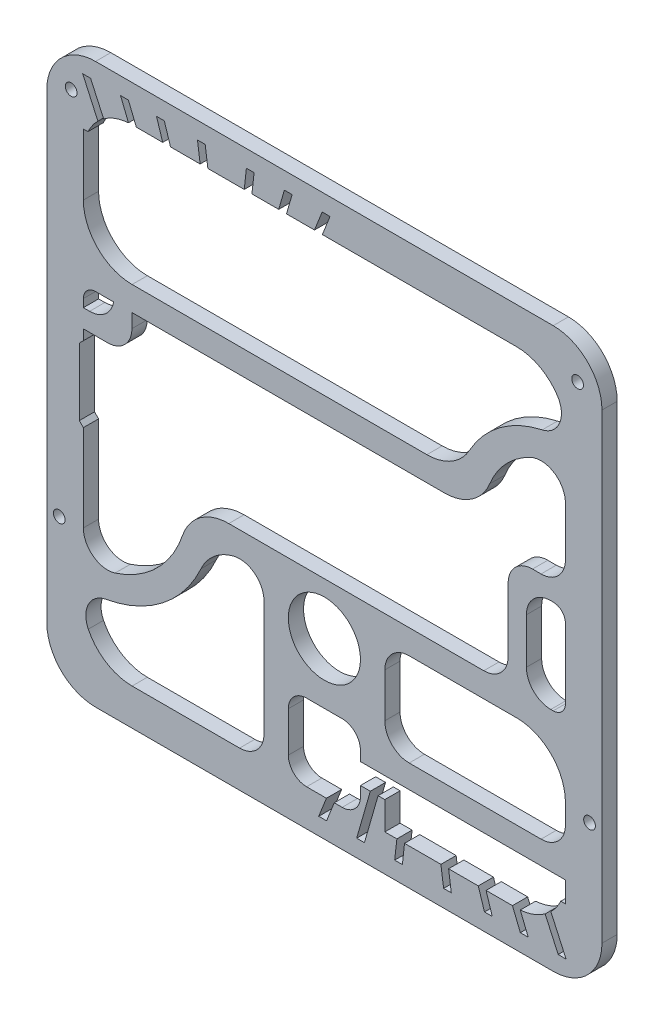
SolidWorks part; units mm, degrees
ref_plane "Front Plane" through (0, 0, 0) normal (0, 0, 1) x (1, 0, 0)
ref_plane "Top Plane" through (0, 0, 0) normal (0, 1, 0) x (1, 0, 0)
ref_plane "Right Plane" through (0, 0, 0) normal (1, 0, 0) x (0, 0, -1)
sketch "Sketch1" plane through (0, 0, 0) normal (0, 0, 1) x (1, 0, 0)
  line L0 (44.642, 21.8842) -> (44.642, 18.0742) construction
  line L1 (-8.1388, 21.8842) -> (49.7286, 21.8842)
  line L2 (-8.1388, 21.8842) -> (-8.1388, -36.406)
  line L3 (-8.1388, -36.406) -> (49.7286, -36.406)
  line L4 (49.7286, 21.8842) -> (49.7286, -36.406)
  line L5 (45.9186, -32.596) -> (-4.3288, -32.596)
  line L6 (45.9186, -32.596) -> (45.9186, 18.0742)
  line L7 (45.9186, 18.0742) -> (-4.3288, 18.0742)
  line L8 (-4.3288, -32.596) -> (-4.3288, 18.0742)
  line L9 (44.642, 19.9792) -> (-35.1587, 19.9792) construction
  line L10 (-4.3288, -31.0517) -> (-8.1388, -31.0517) construction
  line L11 (-6.2338, -31.0517) -> (-6.2338, 6.9585) construction
  line L12 (20.6521, 19.9792) -> (21.1982, 19.9792) construction
  line L13 (-6.2338, -12.887) -> (-6.2338, -25.1298) construction
  line L14 (3.0779, -32.596) -> (3.0779, -36.406) construction
  line L15 (3.0779, -34.501) -> (37.3423, -34.501) construction
  line L17 (49.7286, 15.2205) -> (45.9186, 15.2205) construction
  line L18 (47.8236, 15.2205) -> (47.8236, -0.9437) construction
  line L19 (47.8236, -1.6348) -> (47.8236, 10.608) construction
  line L20 (20.9378, -34.501) -> (20.3916, -34.501) construction
  dimension "D1" = 3.81
  dimension "D2" = 3.81
extrude "Boss-Extrude1" add sketch "Sketch1" along normal blind 1.5875
sketch "Sketch2" plane through (0, 0, 0) normal (0, 0, -1) x (-1, 0, 0)
  line L0 (-45.9186, -32.596) -> (-45.9186, 18.0742) construction
  line L1 (-34.8696, 3.653) -> (4.3288, 3.653)
  line L2 (-45.9186, 3.653) -> (-45.9186, 0.7339)
  line L3 (-37.4096, 1.113) -> (4.3288, 1.113)
  line L4 (4.3288, 3.653) -> (4.3288, 1.113)
  line L5 (4.3288, 18.0742) -> (4.3288, -32.596) construction
  line L6 (-33.4496, 1.113) -> (-36.4496, 1.113) construction
  line L7 (1.2504, -12.887) -> (-36.4496, -12.887) construction
  line L8 (-45.9186, -15.427) -> (-8.8785, -15.427)
  line L9 (-45.9186, -15.427) -> (-45.9186, -12.887)
  line L10 (-45.9186, -12.887) -> (-6.5805, -12.887)
  line L11 (1.357, -21.2563) -> (14.2432, -21.2563) construction
  line L12 (4.3288, -23.7963) -> (4.3288, -26.3363)
  line L13 (-45.9186, 12.162) -> (-45.9186, 9.622)
  arc A0 (-45.9186, 9.622) -> (-37.4096, 1.113) centre (-45.9186, 1.113) cw
  arc A1 (-45.9186, 12.162) -> (-34.8696, 3.653) centre (-45.9186, 0.7339) cw
  arc A2 (4.3288, -23.7963) -> (-6.5805, -12.887) centre (4.3288, -12.887) cw
  arc A3 (-8.8785, -15.427) -> (4.3288, -26.3363) centre (4.3288, -12.887) ccw
  circle A5 centre (1.357, -18.2591) radius 2.9972 construction
  line M5 (-45.9186, -32.596) -> (-45.9186, 18.0742)
  line M7 (4.3288, 18.0742) -> (4.3288, -32.596)
  dimension "D5" = 2.54
  dimension "D1" = 2.54
  dimension "D2" = 2.54
  dimension "D3" = 2.54
  dimension "D4" = 2.54
  dimension "D6" = 2.54
  dimension "D7" = 2.54
extrude "Boss-Extrude2" add sketch "Sketch2" against normal up to surface (1.5875 mm away) contours A1 A0 L3 L1 M5 M7 | L10 L8 M5 M7 region at (15.2704, 3.1385, 0) region at (-3.8086, -25.0663, 0) up to face at (20.7949, -7.2609, 1.5875)
sketch "Sketch3" plane through (0, 0, 0) normal (0, 0, -1) x (-1, 0, 0)
  line L0 (-45.9186, -1.1649) -> (-39.9496, -1.1649)
  line L1 (-45.9186, -12.887) -> (-45.9186, 9.622) construction
  line L2 (-39.9496, -4.387) -> (-39.9496, -11.387) construction
  line L3 (-39.9496, -1.1649) -> (-39.9496, -12.887)
  line L4 (-45.9186, -12.887) -> (-6.5805, -12.887) construction
  line L5 (-39.9496, -12.887) -> (-41.8546, -12.887)
  line L6 (-41.8546, -12.887) -> (-41.8546, -3.0699)
  line L7 (-41.8546, -3.0699) -> (-45.9186, -3.0699)
  line L8 (-45.9186, -3.0699) -> (-45.9186, -1.1649)
  line L9 (-42.9468, 0.7401) -> (-53.4831, 0.7401) construction
  line L10 (-0.7296, 1.113) -> (-0.7296, -2.887)
  line L11 (-37.4096, 1.113) -> (4.3288, 1.113) construction
  line L12 (-1.9996, -2.887) -> (1.2504, -2.887) construction
  line L13 (-0.7296, -2.887) -> (4.3288, -2.887)
  line L14 (4.3288, 1.113) -> (4.3288, -23.7963) construction
  line L15 (4.3288, -2.887) -> (4.3288, -0.982)
  line L16 (4.3288, -0.982) -> (1.1754, -0.982)
  line L17 (1.1754, -0.982) -> (1.1754, 1.113)
  line L18 (1.1754, 1.113) -> (-0.7296, 1.113)
  circle A0 centre (-42.9468, 3.7373) radius 2.9972 construction
  dimension "D1" = 1.905
  dimension "D2" = 1.905
  dimension "D3" = 1.905
  dimension "D4" = 1.905
  dimension "D5" = 1.27
  dimension "D6" = 1.905
extrude "Boss-Extrude3" add sketch "Sketch3" against normal up to surface (1.5875 mm away) up to face at (21.2778, -6.3699, 1.5875)
fillet "Fillet1" radius 5.08 4 edges at (49.7286, -36.406, 0.7937) (-8.1388, -36.406, 0.7937) (-8.1388, 21.8842, 0.7937) (49.7286, 21.8842, 0.7937)
fillet "Fillet2" radius 5.08 10 edges at (8.8785, -15.427, 0.7937) (45.9186, -15.427, 0.7937) (45.9186, -32.596, 0.7937) (-4.3288, -32.596, 0.7937) (34.8696, 3.653, 0.7937) (-4.3288, 3.653, 0.7937) (45.9186, 18.0742, 0.7937) (-4.3288, 18.0742, 0.7937) (6.5805, -12.887, 0.7937) (37.4096, 1.113, 0.7937)
fillet "Fillet3" radius 2.54 11 edges at (41.8546, -3.0699, 0.7938) (39.9496, -12.887, 0.7938) (41.8546, -12.887, 0.7938) (39.9496, -1.1649, 0.7938) (45.9186, -1.1649, 0.7938) (-1.1754, -0.982, 0.7938) (0.7296, -2.887, 0.7938) (45.9186, 9.622, 0.7937) (-4.3288, -26.3363, 0.7937) (-4.3288, -23.7963, 0.7937) (45.9186, 12.162, 0.7937)
fillet "Fillet4" radius 1.27 3 edges at (45.9186, -12.887, 0.7937) (45.9186, -3.0699, 0.7938) (-4.3288, 1.113, 0.7937)
sketch "Sketch5" plane through (0, 0, 0) normal (0, 0, -1) x (-1, 0, 0)
  line L0 (-40.8386, -15.427) -> (-12.5612, -15.427) construction
  line L1 (-27.0941, -15.427) -> (-14.4957, -15.427)
  line L2 (-27.0941, -15.427) -> (-27.0941, -32.596)
  line L3 (-27.0941, -32.596) -> (-14.4957, -32.596)
  line L4 (-14.4957, -15.427) -> (-14.4957, -32.596)
  line L5 (-0.7512, -32.596) -> (-40.8386, -32.596) construction
  line L6 (-24.5541, -18.2972) -> (-27.0941, -18.2972) construction
  line L9 (-17.0357, -18.2972) -> (-14.4957, -18.2972) construction
  circle A1 centre (-20.7949, -18.2972) radius 3.7592 construction
  dimension "D1" = 2.54
extrude "Boss-Extrude4" add sketch "Sketch5" against normal up to surface (1.5875 mm away) up to face at (-3.29, -0.0173, 1.5875)
sketch "Sketch6" plane through (0, 0, 0) normal (0, 0, -1) x (-1, 0, 0)
  circle A0 centre (-20.7949, -18.2972) radius 3.7592 construction
  circle A1 centre (-20.7949, -18.2972) radius 3.7592
extrude "Cut-Extrude2" cut sketch "Sketch6" against normal up to surface (1.5875 mm away) up to face at (6.2356, -24.4396, 1.5875)
sketch "Sketch7" plane through (0, 0, 0) normal (0, 0, -1) x (-1, 0, 0)
  line L0 (-27.0941, -15.427) -> (-27.0941, -32.596) construction
  line L1 (-24.5541, -24.5964) -> (-17.0357, -24.5964)
  line L2 (-24.5541, -24.5964) -> (-24.5541, -32.596)
  line L3 (-24.5541, -32.596) -> (-17.0357, -32.596)
  line L4 (-17.0357, -24.5964) -> (-17.0357, -32.596)
  line L5 (-14.4957, -32.596) -> (-14.4957, -15.427) construction
  line L6 (-0.7512, -32.596) -> (-14.4957, -32.596) construction
  line L7 (-20.7949, -22.0564) -> (-6.5424, -22.0564) construction
  line L8 (-20.7949, -22.0564) -> (-20.7949, -21.3452) construction
  circle A0 centre (-20.7949, -18.2972) radius 3.7592 construction
  dimension "D1" = 2.54
  dimension "D2" = 2.54
  dimension "D3" = 2.54
extrude "Cut-Extrude3" cut sketch "Sketch7" against normal up to surface (1.5875 mm away) up to face at (24.5541, -18.2972, 1.5875)
fillet "Fillet5" radius 1.905 4 edges at (24.5541, -32.596, 0.7937) (17.0357, -32.596, 0.7938) (17.0357, -24.5964, 0.7938) (24.5541, -24.5964, 0.7938)
sketch "Sketch8" plane through (0, 0, 0) normal (0, 0, -1) x (-1, 0, 0)
  line L0 (-45.9186, -27.516) -> (-45.9186, -20.507) construction
  line L1 (-45.9186, -25.103) -> (-27.0941, -25.103)
  line L2 (-45.9186, -25.103) -> (-45.9186, -27.643)
  line L3 (-45.9186, -27.643) -> (-27.0941, -27.643)
  line L4 (-27.0941, -25.103) -> (-27.0941, -27.643)
  line L5 (-27.0941, -15.427) -> (-27.0941, -32.596) construction
  line L6 (-45.7916, -27.643) -> (-20.3916, -27.643) construction
  dimension "D1" = 2.54
extrude "Boss-Extrude5" add sketch "Sketch8" against normal up to surface (1.5875 mm away) up to face at (20.7949, -28.5962, 1.5875)
fillet "Fillet6" radius 2.54 5 edges at (27.0941, -15.427, 0.7937) (14.4957, -15.427, 0.7937) (14.4957, -32.596, 0.7937) (27.0941, -25.103, 0.7937) (45.9186, -25.103, 0.7937)
sketch "Sketch4" plane through (0, 0, 0) normal (0, 0, -1) x (-1, 0, 0)
  line L0 (3.2504, -2.887) -> (4.7504, -4.387) construction
  line L1 (4.7504, -11.387) -> (3.2504, -12.887) construction
  line L2 (3.2504, -2.887) -> (4.7504, -4.387)
  line L3 (4.7504, -11.387) -> (3.2504, -12.887)
  line L4 (4.7504, -4.387) -> (4.7504, -11.387) construction
  line L5 (4.7504, -4.387) -> (4.7504, -11.387)
  line L6 (3.2504, -2.887) -> (3.2504, -12.887)
  line L32 (4.2018, 13.1212) -> (4.2018, 15.0262)
  line L33 (4.2018, 15.0262) -> (1.9539, 15.0262)
  line L34 (1.9539, 15.0262) -> (4.2018, 19.9792)
  line L35 (4.2018, 19.9792) -> (3.6556, 19.9792)
  line L36 (3.6556, 19.9792) -> (1.4078, 15.0262)
  line L37 (1.4078, 15.0262) -> (-1.7417, 15.0262)
  line L38 (-1.7417, 15.0262) -> (0.2648, 19.9792)
  line L39 (0.2648, 19.9792) -> (-0.2814, 19.9792)
  line L40 (-0.2814, 19.9792) -> (-2.2879, 15.0262)
  line L41 (-2.2879, 15.0262) -> (-5.0437, 15.0262)
  line L42 (-5.0437, 15.0262) -> (-3.469, 19.9792)
  line L43 (-3.469, 19.9792) -> (-4.0152, 19.9792)
  line L44 (-4.0152, 19.9792) -> (-5.5899, 15.0262)
  line L45 (-5.5899, 15.0262) -> (-8.3965, 15.0262)
  line L46 (-8.3965, 15.0262) -> (-7.7108, 19.9792)
  line L47 (-7.7108, 19.9792) -> (-8.257, 19.9792)
  line L48 (-8.257, 19.9792) -> (-8.9427, 15.0262)
  line L49 (-8.9427, 15.0262) -> (-12.2319, 15.0262)
  line L50 (-12.2319, 15.0262) -> (-12.7781, 19.9792)
  line L51 (-12.7781, 19.9792) -> (-13.3242, 19.9792)
  line L52 (-13.3242, 19.9792) -> (-12.7781, 15.0262)
  line L53 (-12.7781, 15.0262) -> (-15.2926, 15.0262)
  line L54 (-15.2926, 15.0262) -> (-16.7151, 19.9792)
  line L55 (-16.7151, 19.9792) -> (-17.2612, 19.9792)
  line L56 (-17.2612, 19.9792) -> (-15.8388, 15.0262)
  line L57 (-15.8388, 15.0262) -> (-18.6963, 15.0262)
  line L58 (-18.6963, 15.0262) -> (-20.6521, 19.9792)
  line L59 (-20.6521, 19.9792) -> (-21.1982, 19.9792)
  line L60 (-21.1982, 19.9792) -> (-19.2425, 15.0262)
  line L61 (-19.2425, 15.0262) -> (-21.1982, 15.0262)
  line L62 (-21.1982, 15.0262) -> (-21.1982, 13.1212)
  line L63 (-21.1982, 13.1212) -> (4.2018, 13.1212)
  line L64 (4.2018, 13.1212) -> (4.2018, 15.0262) construction
  line L65 (4.2018, 15.0262) -> (1.9539, 15.0262) construction
  line L66 (1.9539, 15.0262) -> (4.2018, 19.9792) construction
  line L67 (4.2018, 19.9792) -> (3.6556, 19.9792) construction
  line L68 (3.6556, 19.9792) -> (1.4078, 15.0262) construction
  line L69 (1.4078, 15.0262) -> (-1.7417, 15.0262) construction
  line L70 (-1.7417, 15.0262) -> (0.2648, 19.9792) construction
  line L71 (0.2648, 19.9792) -> (-0.2814, 19.9792) construction
  line L72 (-0.2814, 19.9792) -> (-2.2879, 15.0262) construction
  line L73 (-2.2879, 15.0262) -> (-5.0437, 15.0262) construction
  line L74 (-5.0437, 15.0262) -> (-3.469, 19.9792) construction
  line L75 (-3.469, 19.9792) -> (-4.0152, 19.9792) construction
  line L76 (-4.0152, 19.9792) -> (-5.5899, 15.0262) construction
  line L77 (-5.5899, 15.0262) -> (-8.3965, 15.0262) construction
  line L78 (-8.3965, 15.0262) -> (-7.7108, 19.9792) construction
  line L79 (-7.7108, 19.9792) -> (-8.257, 19.9792) construction
  line L80 (-8.257, 19.9792) -> (-8.9427, 15.0262) construction
  line L81 (-8.9427, 15.0262) -> (-12.2319, 15.0262) construction
  line L82 (-12.2319, 15.0262) -> (-12.7781, 19.9792) construction
  line L83 (-12.7781, 19.9792) -> (-13.3242, 19.9792) construction
  line L84 (-13.3242, 19.9792) -> (-12.7781, 15.0262) construction
  line L85 (-12.7781, 15.0262) -> (-15.2926, 15.0262) construction
  line L86 (-15.2926, 15.0262) -> (-16.7151, 19.9792) construction
  line L87 (-16.7151, 19.9792) -> (-17.2612, 19.9792) construction
  line L88 (-17.2612, 19.9792) -> (-15.8388, 15.0262) construction
  line L89 (-15.8388, 15.0262) -> (-18.6963, 15.0262) construction
  line L90 (-18.6963, 15.0262) -> (-20.6521, 19.9792) construction
  line L91 (-20.6521, 19.9792) -> (-21.1982, 19.9792) construction
  line L92 (-21.1982, 19.9792) -> (-19.2425, 15.0262) construction
  line L93 (-19.2425, 15.0262) -> (-21.1982, 15.0262) construction
  line L94 (-21.1982, 15.0262) -> (-21.1982, 13.1212) construction
  line L95 (-21.1982, 13.1212) -> (4.2018, 13.1212) construction
  line L96 (-45.7916, -27.643) -> (-45.7916, -29.548)
  line L97 (-45.7916, -29.548) -> (-43.5438, -29.548)
  line L98 (-43.5438, -29.548) -> (-45.7916, -34.501)
  line L99 (-45.7916, -34.501) -> (-45.2455, -34.501)
  line L100 (-45.2455, -34.501) -> (-42.9976, -29.548)
  line L101 (-42.9976, -29.548) -> (-39.8482, -29.548)
  line L102 (-39.8482, -29.548) -> (-41.8546, -34.501)
  line L103 (-41.8546, -34.501) -> (-41.3085, -34.501)
  line L104 (-41.3085, -34.501) -> (-39.302, -29.548)
  line L105 (-39.302, -29.548) -> (-36.5462, -29.548)
  line L106 (-36.5462, -29.548) -> (-38.1208, -34.501)
  line L107 (-38.1208, -34.501) -> (-37.5747, -34.501)
  line L108 (-37.5747, -34.501) -> (-36, -29.548)
  line L109 (-36, -29.548) -> (-33.1934, -29.548)
  line L110 (-33.1934, -29.548) -> (-33.879, -34.501)
  line L111 (-33.879, -34.501) -> (-33.3329, -34.501)
  line L112 (-33.3329, -34.501) -> (-32.6472, -29.548)
  line L113 (-32.6472, -29.548) -> (-29.358, -29.548)
  line L114 (-29.358, -29.548) -> (-28.8118, -34.501)
  line L115 (-28.8118, -34.501) -> (-28.2656, -34.501)
  line L116 (-28.2656, -34.501) -> (-28.8118, -29.548)
  line L117 (-28.8118, -29.548) -> (-26.2973, -29.548)
  line L118 (-26.2973, -29.548) -> (-24.8748, -34.501)
  line L119 (-24.8748, -34.501) -> (-24.3286, -34.501)
  line L120 (-24.3286, -34.501) -> (-25.7511, -29.548)
  line L121 (-25.7511, -29.548) -> (-22.8935, -29.548)
  line L122 (-22.8935, -29.548) -> (-20.9378, -34.501)
  line L123 (-20.9378, -34.501) -> (-20.3916, -34.501)
  line L124 (-20.3916, -34.501) -> (-22.3474, -29.548)
  line L125 (-22.3474, -29.548) -> (-20.3916, -29.548)
  line L126 (-20.3916, -29.548) -> (-20.3916, -27.643)
  line L127 (-20.3916, -27.643) -> (-45.7916, -27.643)
  line L128 (-45.7916, -27.643) -> (-45.7916, -29.548) construction
  line L129 (-45.7916, -29.548) -> (-43.5438, -29.548) construction
  line L130 (-43.5438, -29.548) -> (-45.7916, -34.501) construction
  line L131 (-45.7916, -34.501) -> (-45.2455, -34.501) construction
  line L132 (-45.2455, -34.501) -> (-42.9976, -29.548) construction
  line L133 (-42.9976, -29.548) -> (-39.8482, -29.548) construction
  line L134 (-39.8482, -29.548) -> (-41.8546, -34.501) construction
  line L135 (-41.8546, -34.501) -> (-41.3085, -34.501) construction
  line L136 (-41.3085, -34.501) -> (-39.302, -29.548) construction
  line L137 (-39.302, -29.548) -> (-36.5462, -29.548) construction
  line L138 (-36.5462, -29.548) -> (-38.1208, -34.501) construction
  line L139 (-38.1208, -34.501) -> (-37.5747, -34.501) construction
  line L140 (-37.5747, -34.501) -> (-36, -29.548) construction
  line L141 (-36, -29.548) -> (-33.1934, -29.548) construction
  line L142 (-33.1934, -29.548) -> (-33.879, -34.501) construction
  line L143 (-33.879, -34.501) -> (-33.3329, -34.501) construction
  line L144 (-33.3329, -34.501) -> (-32.6472, -29.548) construction
  line L145 (-32.6472, -29.548) -> (-29.358, -29.548) construction
  line L146 (-29.358, -29.548) -> (-28.8118, -34.501) construction
  line L147 (-28.8118, -34.501) -> (-28.2656, -34.501) construction
  line L148 (-28.2656, -34.501) -> (-28.8118, -29.548) construction
  line L149 (-28.8118, -29.548) -> (-26.2973, -29.548) construction
  line L150 (-26.2973, -29.548) -> (-24.8748, -34.501) construction
  line L151 (-24.8748, -34.501) -> (-24.3286, -34.501) construction
  line L152 (-24.3286, -34.501) -> (-25.7511, -29.548) construction
  line L153 (-25.7511, -29.548) -> (-22.8935, -29.548) construction
  line L154 (-22.8935, -29.548) -> (-20.9378, -34.501) construction
  line L155 (-20.9378, -34.501) -> (-20.3916, -34.501) construction
  line L156 (-20.3916, -34.501) -> (-22.3474, -29.548) construction
  line L157 (-22.3474, -29.548) -> (-20.3916, -29.548) construction
  line L158 (-20.3916, -29.548) -> (-20.3916, -27.643) construction
  line L159 (-20.3916, -27.643) -> (-45.7916, -27.643) construction
  line L263 (4.3288, 12.9942) -> (4.3288, 15.1532)
  line L264 (4.3288, 15.1532) -> (2.151, 15.1532)
  line L265 (2.151, 15.1532) -> (4.3989, 20.1062)
  line L266 (4.3989, 20.1062) -> (3.5738, 20.1062)
  line L267 (3.5738, 20.1062) -> (1.3259, 15.1532)
  line L268 (1.3259, 15.1532) -> (-1.5532, 15.1532)
  line L269 (-1.5532, 15.1532) -> (0.4532, 20.1062)
  line L270 (0.4532, 20.1062) -> (-0.367, 20.1062)
  line L271 (-0.367, 20.1062) -> (-2.3735, 15.1532)
  line L272 (-2.3735, 15.1532) -> (-4.8701, 15.1532)
  line L273 (-4.8701, 15.1532) -> (-3.2954, 20.1062)
  line L274 (-3.2954, 20.1062) -> (-4.1081, 20.1062)
  line L275 (-4.1081, 20.1062) -> (-5.6828, 15.1532)
  line L276 (-5.6828, 15.1532) -> (-8.2507, 15.1532)
  line L277 (-8.2507, 15.1532) -> (-7.565, 20.1062)
  line L278 (-7.565, 20.1062) -> (-8.3676, 20.1062)
  line L279 (-8.3676, 20.1062) -> (-9.0533, 15.1532)
  line L280 (-9.0533, 15.1532) -> (-12.1181, 15.1532)
  line L281 (-12.1181, 15.1532) -> (-12.6643, 20.1062)
  line L282 (-12.6643, 20.1062) -> (-13.466, 20.1062)
  line L283 (-13.466, 20.1062) -> (-12.9198, 15.1532)
  line L284 (-12.9198, 15.1532) -> (-15.1969, 15.1532)
  line L285 (-15.1969, 15.1532) -> (-16.6194, 20.1062)
  line L286 (-16.6194, 20.1062) -> (-17.4298, 20.1062)
  line L287 (-17.4298, 20.1062) -> (-16.0074, 15.1532)
  line L288 (-16.0074, 15.1532) -> (-18.6099, 15.1532)
  line L289 (-18.6099, 15.1532) -> (-20.5657, 20.1062)
  line L290 (-20.5657, 20.1062) -> (-21.3849, 20.1062)
  line L291 (-21.3849, 20.1062) -> (-19.4292, 15.1532)
  line L292 (-19.4292, 15.1532) -> (-21.3252, 15.1532)
  line L293 (-21.3252, 15.1532) -> (-21.3252, 12.9942)
  line L294 (-21.3252, 12.9942) -> (4.3288, 12.9942)
  line L295 (-45.9186, -27.516) -> (-45.9186, -29.675)
  line L296 (-45.9186, -29.675) -> (-43.7409, -29.675)
  line L297 (-43.7409, -29.675) -> (-45.9887, -34.628)
  line L298 (-45.9887, -34.628) -> (-45.1636, -34.628)
  line L299 (-45.1636, -34.628) -> (-42.9158, -29.675)
  line L300 (-42.9158, -29.675) -> (-40.0367, -29.675)
  line L301 (-40.0367, -29.675) -> (-42.0431, -34.628)
  line L302 (-42.0431, -34.628) -> (-41.2229, -34.628)
  line L303 (-41.2229, -34.628) -> (-39.2164, -29.675)
  line L304 (-39.2164, -29.675) -> (-36.7198, -29.675)
  line L305 (-36.7198, -29.675) -> (-38.2945, -34.628)
  line L306 (-38.2945, -34.628) -> (-37.4818, -34.628)
  line L307 (-37.4818, -34.628) -> (-35.9071, -29.675)
  line L308 (-35.9071, -29.675) -> (-33.3392, -29.675)
  line L309 (-33.3392, -29.675) -> (-34.0248, -34.628)
  line L310 (-34.0248, -34.628) -> (-33.2222, -34.628)
  line L311 (-33.2222, -34.628) -> (-32.5366, -29.675)
  line L312 (-32.5366, -29.675) -> (-29.4717, -29.675)
  line L313 (-29.4717, -29.675) -> (-28.9256, -34.628)
  line L314 (-28.9256, -34.628) -> (-28.1239, -34.628)
  line L315 (-28.1239, -34.628) -> (-28.67, -29.675)
  line L316 (-28.67, -29.675) -> (-26.3929, -29.675)
  line L317 (-26.3929, -29.675) -> (-24.9705, -34.628)
  line L318 (-24.9705, -34.628) -> (-24.16, -34.628)
  line L319 (-24.16, -34.628) -> (-25.5825, -29.675)
  line L320 (-25.5825, -29.675) -> (-22.9799, -29.675)
  line L321 (-22.9799, -29.675) -> (-21.0242, -34.628)
  line L322 (-21.0242, -34.628) -> (-20.205, -34.628)
  line L323 (-20.205, -34.628) -> (-22.1607, -29.675)
  line L324 (-22.1607, -29.675) -> (-20.2646, -29.675)
  line L325 (-20.2646, -29.675) -> (-20.2646, -27.516)
  line L326 (-20.2646, -27.516) -> (-45.9186, -27.516)
  dimension "D1" = 0
  dimension "D2" = 0
  dimension "D3" = 0.127
  dimension "D4" = 0.127
extrude "Cut-Extrude1" cut sketch "Sketch4" against normal up to surface (1.5875 mm away) up to face at (36.2546, -20.5167, 1.5875)
sketch "Sketch9" plane through (0, 0, 0) normal (0, 0, -1) x (-1, 0, 0)
  circle A0 centre (-47.1886, 18.0742) radius 0.6096 construction
  circle A1 centre (5.5988, 18.0742) radius 0.6096 construction
  circle A2 centre (6.8434, -21.0912) radius 0.6096 construction
  circle A3 centre (-48.4332, -21.0912) radius 0.6096 construction
  circle A4 centre (-47.1886, 18.0742) radius 0.6096
  circle A5 centre (5.5988, 18.0742) radius 0.6096
  circle A6 centre (6.8434, -21.0912) radius 0.6096
  circle A7 centre (-48.4332, -21.0912) radius 0.6096
extrude "Cut-Extrude4" cut sketch "Sketch9" against normal up to surface (1.5875 mm away) up to face at (31.0514, -31.8182, 1.5875)
